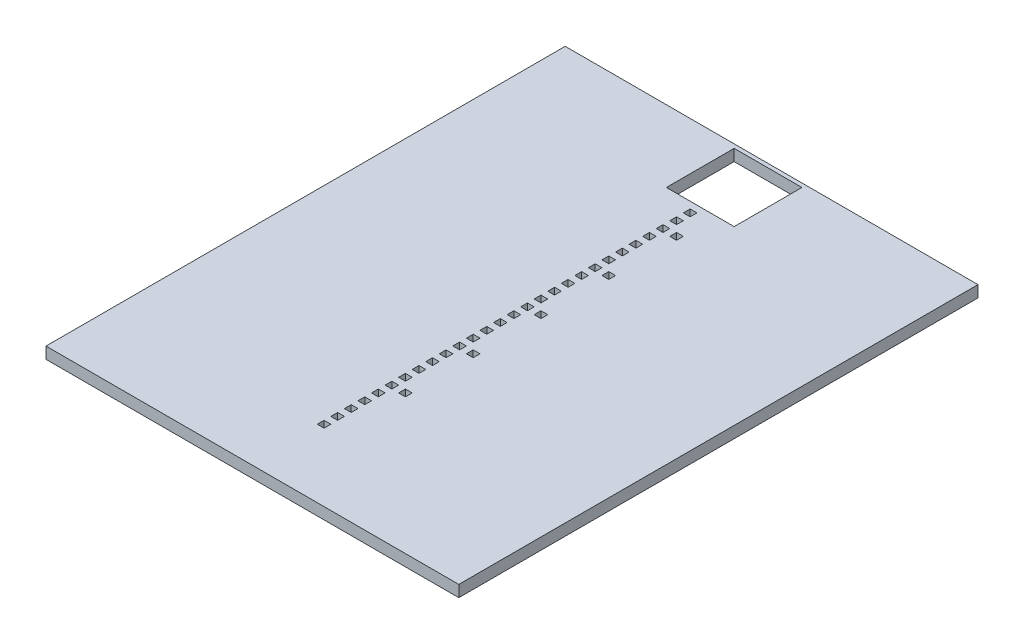
SolidWorks part; units mm, degrees
ref_plane "Front Plane" through (0, 0, 0) normal (0, 0, 1) x (1, 0, 0)
ref_plane "Top Plane" through (0, 0, 0) normal (0, 1, 0) x (1, 0, 0)
ref_plane "Right Plane" through (0, 0, 0) normal (1, 0, 0) x (0, 0, -1)
sketch "Sketch1" plane through (0, 0, 0) normal (0, 1, 0) x (1, 0, 0)
  line L0 (-5, -90) -> (5, -90)
  line L1 (-305, 55.73) -> (304, 55.73)
  line L2 (-305, 55.73) -> (-305, -710.27)
  line L3 (-305, -710.27) -> (304, -710.27)
  line L4 (304, 55.73) -> (304, -710.27)
  line L5 (-50, 50) -> (50, 50)
  line L6 (-50, 50) -> (-50, -50)
  line L7 (-50, -50) -> (50, -50)
  line L8 (50, 50) -> (50, -50)
  line L9 (-5, -60) -> (5, -60)
  line L10 (-5, -60) -> (-5, -70)
  line L11 (-5, -70) -> (5, -70)
  line L12 (5, -60) -> (5, -70)
  line L13 (5, -80) -> (5, -90)
  line L14 (-5, -80) -> (5, -80)
  line L15 (-5, -80) -> (-5, -90)
  line L16 (-5, -110) -> (5, -110)
  line L17 (5, -100) -> (5, -110)
  line L18 (-5, -100) -> (5, -100)
  line L19 (-5, -100) -> (-5, -110)
  line L20 (-5, -130) -> (5, -130)
  line L21 (5, -120) -> (5, -130)
  line L22 (-5, -120) -> (5, -120)
  line L23 (-5, -120) -> (-5, -130)
  line L24 (-5, -150) -> (5, -150)
  line L25 (5, -140) -> (5, -150)
  line L26 (-5, -140) -> (5, -140)
  line L27 (-5, -140) -> (-5, -150)
  line L28 (-5, -170) -> (5, -170)
  line L29 (5, -160) -> (5, -170)
  line L30 (-5, -160) -> (5, -160)
  line L31 (-5, -160) -> (-5, -170)
  line L32 (-5, -190) -> (5, -190)
  line L33 (5, -180) -> (5, -190)
  line L34 (-5, -180) -> (5, -180)
  line L35 (-5, -180) -> (-5, -190)
  line L36 (-5, -210) -> (5, -210)
  line L37 (5, -200) -> (5, -210)
  line L38 (-5, -200) -> (5, -200)
  line L39 (-5, -200) -> (-5, -210)
  line L40 (-5, -230) -> (5, -230)
  line L41 (5, -220) -> (5, -230)
  line L42 (-5, -220) -> (5, -220)
  line L43 (-5, -220) -> (-5, -230)
  line L44 (-5, -250) -> (5, -250)
  line L45 (5, -240) -> (5, -250)
  line L46 (-5, -240) -> (5, -240)
  line L47 (-5, -240) -> (-5, -250)
  line L48 (-5, -270) -> (5, -270)
  line L49 (5, -260) -> (5, -270)
  line L50 (-5, -260) -> (5, -260)
  line L51 (-5, -260) -> (-5, -270)
  line L52 (-5, -290) -> (5, -290)
  line L53 (5, -280) -> (5, -290)
  line L54 (-5, -280) -> (5, -280)
  line L55 (-5, -280) -> (-5, -290)
  line L56 (-5, -310) -> (5, -310)
  line L57 (5, -300) -> (5, -310)
  line L58 (-5, -300) -> (5, -300)
  line L59 (-5, -300) -> (-5, -310)
  line L60 (-5, -330) -> (5, -330)
  line L61 (5, -320) -> (5, -330)
  line L62 (-5, -320) -> (5, -320)
  line L63 (-5, -320) -> (-5, -330)
  line L64 (-5, -350) -> (5, -350)
  line L65 (5, -340) -> (5, -350)
  line L66 (-5, -340) -> (5, -340)
  line L67 (-5, -340) -> (-5, -350)
  line L68 (-5, -370) -> (5, -370)
  line L69 (5, -360) -> (5, -370)
  line L70 (-5, -360) -> (5, -360)
  line L71 (-5, -360) -> (-5, -370)
  line L72 (-5, -390) -> (5, -390)
  line L73 (5, -380) -> (5, -390)
  line L74 (-5, -380) -> (5, -380)
  line L75 (-5, -380) -> (-5, -390)
  line L76 (-5, -410) -> (5, -410)
  line L77 (5, -400) -> (5, -410)
  line L78 (-5, -400) -> (5, -400)
  line L79 (-5, -400) -> (-5, -410)
  line L80 (-5, -430) -> (5, -430)
  line L81 (5, -420) -> (5, -430)
  line L82 (-5, -420) -> (5, -420)
  line L83 (-5, -420) -> (-5, -430)
  line L84 (-5, -450) -> (5, -450)
  line L85 (5, -440) -> (5, -450)
  line L86 (-5, -440) -> (5, -440)
  line L87 (-5, -440) -> (-5, -450)
  line L88 (-5, -470) -> (5, -470)
  line L89 (5, -460) -> (5, -470)
  line L90 (-5, -460) -> (5, -460)
  line L91 (-5, -460) -> (-5, -470)
  line L92 (-5, -490) -> (5, -490)
  line L93 (5, -480) -> (5, -490)
  line L94 (-5, -480) -> (5, -480)
  line L95 (-5, -480) -> (-5, -490)
  line L96 (-5, -510) -> (5, -510)
  line L97 (5, -500) -> (5, -510)
  line L98 (-5, -500) -> (5, -500)
  line L99 (-5, -500) -> (-5, -510)
  line L100 (-5, -530) -> (5, -530)
  line L101 (5, -520) -> (5, -530)
  line L102 (-5, -520) -> (5, -520)
  line L103 (-5, -520) -> (-5, -530)
  line L104 (-5, -550) -> (5, -550)
  line L105 (5, -540) -> (5, -550)
  line L106 (-5, -540) -> (5, -540)
  line L107 (-5, -540) -> (-5, -550)
  line L108 (-5, -570) -> (5, -570)
  line L109 (5, -560) -> (5, -570)
  line L110 (-5, -560) -> (5, -560)
  line L111 (-5, -560) -> (-5, -570)
  line L112 (-5, -590) -> (5, -590)
  line L113 (5, -580) -> (5, -590)
  line L114 (-5, -580) -> (5, -580)
  line L115 (-5, -580) -> (-5, -590)
  line L116 (-5, -610) -> (5, -610)
  line L117 (5, -600) -> (5, -610)
  line L118 (-5, -600) -> (5, -600)
  line L119 (-5, -600) -> (-5, -610)
  line L121 (15, -100) -> (25, -100)
  line L122 (15, -100) -> (15, -110)
  line L123 (25, -100) -> (25, -110)
  line L124 (15, -110) -> (25, -110)
  line L125 (15, -200) -> (25, -200)
  line L126 (15, -200) -> (15, -210)
  line L127 (15, -210) -> (25, -210)
  line L128 (25, -200) -> (25, -210)
  line L129 (15, -300) -> (25, -300)
  line L130 (15, -300) -> (15, -310)
  line L131 (25, -300) -> (25, -310)
  line L132 (15, -310) -> (25, -310)
  line L133 (15, -400) -> (25, -400)
  line L134 (25, -400) -> (25, -410)
  line L135 (15, -410) -> (25, -410)
  line L136 (15, -400) -> (15, -410)
  line L137 (15, -500) -> (25, -500)
  line L138 (25, -500) -> (25, -510)
  line L139 (15, -510) -> (25, -510)
  line L140 (15, -500) -> (15, -510)
  dimension "D1" = 609
  dimension "D2" = 766
  dimension "D3" = 100
  dimension "D4" = 100
  dimension "D5" = 50
  dimension "D6" = 50
  dimension "D7" = 5.73
  dimension "D8" = 255
  dimension "D9" = 10
  dimension "D10" = 10
  dimension "D11" = 60
  dimension "D12" = 5
  dimension "D14" = 80
  dimension "D15" = 2
  dimension "D16" = 100
  dimension "D17" = 10
  dimension "D19" = 100
  dimension "D20" = 10
  dimension "D22" = 100
  dimension "D23" = 10
  dimension "D24" = 2
  dimension "D25" = 100
  dimension "D26" = 10
  dimension "D28" = 100
  dimension "D29" = 10
  dimension "D13" = 28
  dimension "D18" = 2
  dimension "D21" = 2
  dimension "D27" = 2
extrude "Boss-Extrude1" add sketch "Sketch1" along normal blind 17
